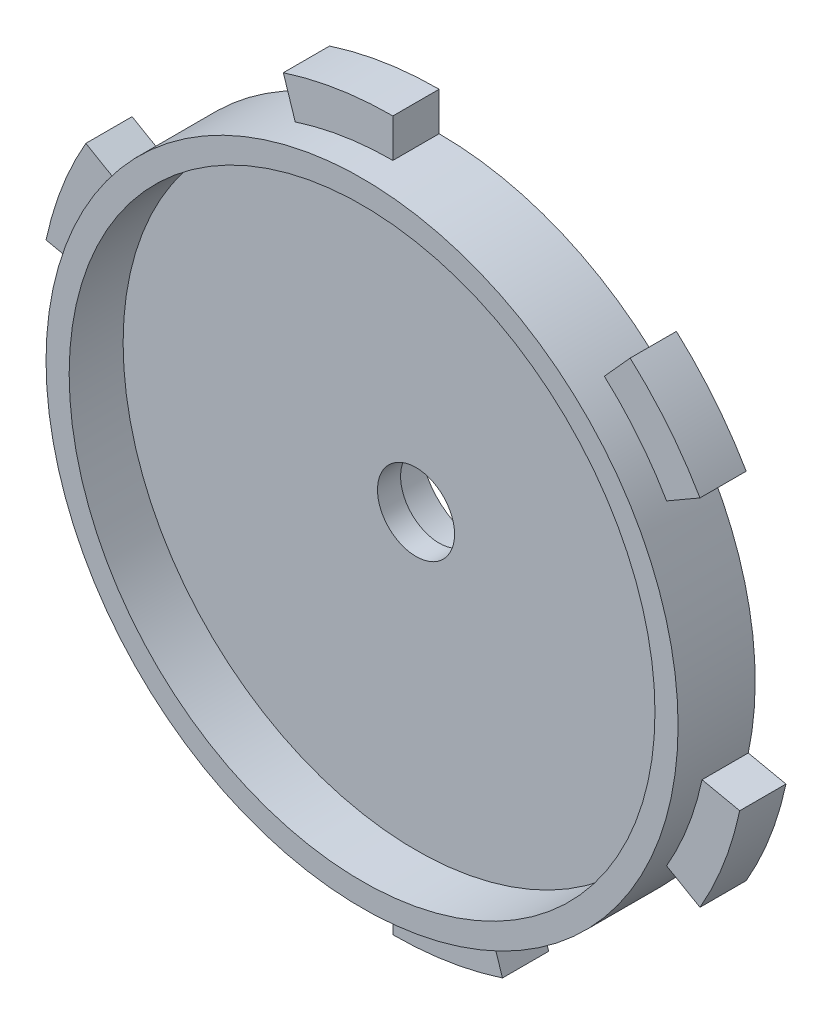
SolidWorks part; units mm, degrees
ref_plane "Front Plane" through (0, 0, 0) normal (0, 0, 1) x (1, 0, 0)
ref_plane "Top Plane" through (0, 0, 0) normal (0, 1, 0) x (1, 0, 0)
ref_plane "Right Plane" through (0, 0, 0) normal (1, 0, 0) x (0, 0, -1)
sketch "Sketch1" plane through (0, 0, 0) normal (0, 0, 1) x (1, 0, 0)
  circle A0 centre (0, 0) radius 41
  circle A1 centre (0, 0) radius 5
  dimension "D1" = 82
  dimension "D2" = 10
extrude "Boss-Extrude2" add sketch "Sketch1" along normal blind 10 contours A1 | A0 A1 region at (-39.8403, 0, 0) region at (0, 0, 0)
shell "Shell2" thickness 3 removed face at (41, 0, 10)
extrude "Cut-Extrude1" cut sketch "Sketch1<4>" along normal through all both and the other way through all contours A1 region at (0, 0, 0)
sketch "Sketch1<4>" plane through (0, 0, 0) normal (0, 0, 1) x (1, 0, 0) same geometry as "Sketch1"
sketch "Sketch3" plane through (0, 0, 0) normal (0, 0, -1) x (-1, 0, 0)
  circle A0 centre (0, 0) radius 8
  circle A1 centre (0, 0) radius 10
  dimension "D1" = 16
  dimension "D2" = 20
extrude "Boss-Extrude4" add sketch "Sketch3" along normal blind 5.5
sketch "Sketch4" plane through (0, 0, 0) normal (0, 0, -1) x (-1, 0, 0)
  line L0 (0, 46) -> (0, 41)
  line L1 (14.2148, 43.7486) -> (12.6697, 38.9933)
  line L2 (39.8372, 23) -> (35.507, 20.5)
  line L3 (44.9948, 9.5639) -> (40.1041, 8.5244)
  line L4 (39.8372, -23) -> (35.507, -20.5)
  line L5 (30.78, -34.1847) -> (27.4344, -30.4689)
  line L6 (0, -46) -> (0, -41)
  line L7 (-14.2148, -43.7486) -> (-12.6697, -38.9933)
  line L8 (-39.8372, -23) -> (-35.507, -20.5)
  line L9 (-44.9948, -9.5639) -> (-40.1041, -8.5244)
  line L10 (-39.8372, 23) -> (-35.507, 20.5)
  line L11 (-30.78, 34.1847) -> (-27.4344, 30.4689)
  arc A0 (0, 41) -> (12.6697, 38.9933) centre (0, 0) cw
  circle A1 centre (0, 0) radius 41 construction
  arc A2 (0, 46) -> (14.2148, 43.7486) centre (0, 0) cw
  arc A3 (39.8372, 23) -> (44.9948, 9.5639) centre (0, 0) cw
  arc A4 (35.507, 20.5) -> (40.1041, 8.5244) centre (0, 0) cw
  arc A5 (39.8372, -23) -> (30.78, -34.1847) centre (0, 0) cw
  arc A6 (35.507, -20.5) -> (27.4344, -30.4689) centre (0, 0) cw
  arc A7 (0, -46) -> (-14.2148, -43.7486) centre (0, 0) cw
  arc A8 (0, -41) -> (-12.6697, -38.9933) centre (0, 0) cw
  arc A9 (-39.8372, -23) -> (-44.9948, -9.5639) centre (0, 0) cw
  arc A10 (-35.507, -20.5) -> (-40.1041, -8.5244) centre (0, 0) cw
  arc A11 (-39.8372, 23) -> (-30.78, 34.1847) centre (0, 0) cw
  arc A12 (-35.507, 20.5) -> (-27.4344, 30.4689) centre (0, 0) cw
  point P31 (0, 0)
  dimension "D1" = 46
  dimension "D2" = 5
  dimension "D3" = 5
  dimension "D4" = 14.392
extrude "Boss-Extrude5" add sketch "Sketch4" against normal blind 6
